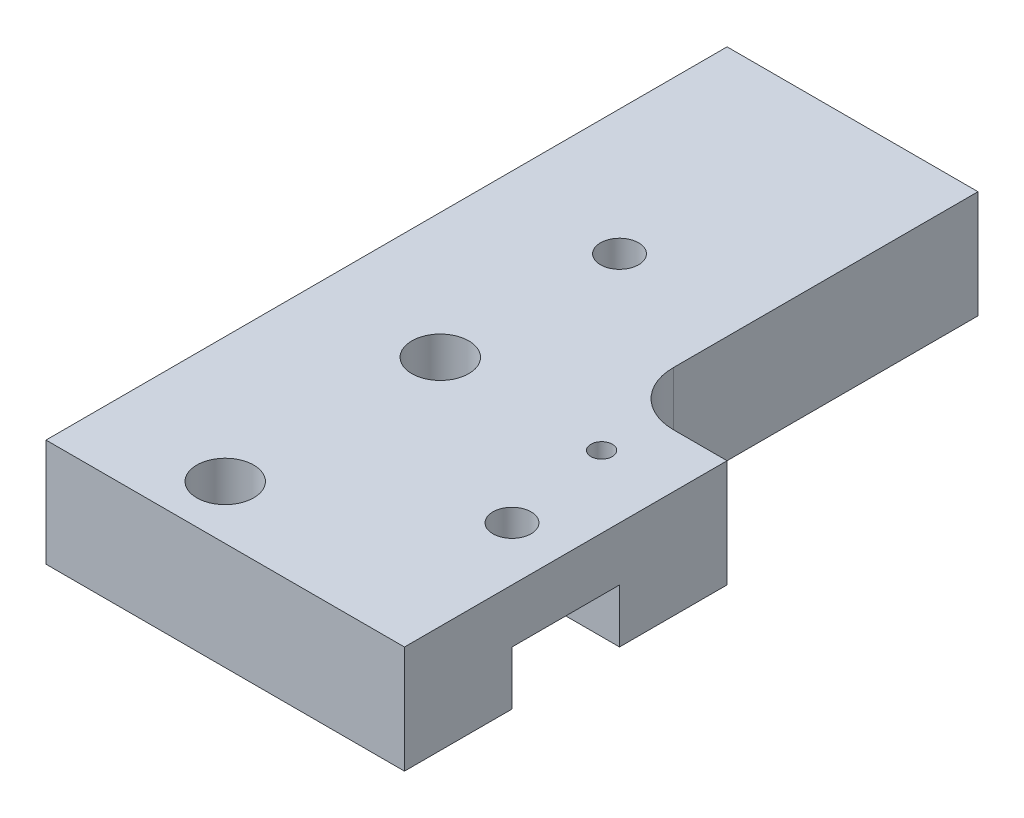
SolidWorks part; units mm, degrees
material "6061-T6 (SS)"
ref_plane "Front" through (0, 0, 0) normal (0, 0, 1) x (1, 0, 0)
ref_plane "Top" through (0, 0, 0) normal (0, 1, 0) x (1, 0, 0)
ref_plane "Right" through (0, 0, 0) normal (1, 0, 0) x (0, 0, -1)
sketch "Sketch1" plane through (0, 0, 0) normal (0, 1, 0) x (1, 0, 0)
  line L1 (-31.75, -28.575) -> (31.75, -28.575)
  line L2 (-31.75, -28.575) -> (-31.75, 28.575)
  line L3 (-31.75, 28.575) -> (31.75, 28.575)
  line L4 (31.75, -28.575) -> (31.75, 28.575)
  line L5 (-31.75, -28.575) -> (31.75, 28.575) construction
  line L6 (-31.75, 28.575) -> (31.75, -28.575) construction
  point P0 (0, 0)
  dimension "D1" = 63.5
  dimension "D2" = 57.15
extrude "Boss-Extrude1" add sketch "Sketch1" along normal blind 19.05
sketch "Sketch2" plane through (0, 0, 0) normal (0, -1, 0) x (1, 0, 0)
  line L0 (31.75, 28.575) -> (31.75, -28.575) construction
  line L1 (-31.75, -9.525) -> (31.75, -9.525)
  line L2 (-31.75, -9.525) -> (-31.75, 9.525)
  line L3 (-31.75, 9.525) -> (31.75, 9.525)
  line L4 (31.75, -9.525) -> (31.75, 9.525)
  line L5 (-31.75, -9.525) -> (31.75, 9.525) construction
  line L6 (-31.75, 9.525) -> (31.75, -9.525) construction
  point P0 (0, 0)
  dimension "D1" = 19.05
extrude "Cut-Extrude1" cut sketch "Sketch2" against normal blind 9.525
sketch "Sketch3" plane through (0, 0, 0) normal (0, -1, 0) x (1, 0, 0)
  line L0 (-31.75, 28.575) -> (31.75, 28.575) construction
  line L1 (3.175, 28.575) -> (15.875, 28.575)
  line L2 (3.175, 28.575) -> (3.175, -28.575)
  line L3 (3.175, -28.575) -> (15.875, -28.575)
  line L4 (15.875, 28.575) -> (15.875, -28.575)
  line L5 (31.75, -28.575) -> (-31.75, -28.575) construction
  line L6 (31.75, 28.575) -> (31.75, 9.525) construction
  dimension "D1" = 12.7
  dimension "D2" = 15.875
extrude "Cut-Extrude2" [suppressed] cut sketch "Sketch3" against normal up to surface (6.35 mm away) up to face at (0, 9.525, 0)
sketch "Sketch4" plane through (0, 9.525, 0) normal (0, -1, 0) x (1, 0, 0)
  line L0 (31.75, 0) -> (22.225, 0) construction
  line L1 (31.75, -9.525) -> (31.75, 9.525) construction
  line L2 (9.525, 28.575) -> (9.525, 19.05) construction
  dimension "D1" = 9.525
sketch "Sketch7" plane through (0, 0, 0) normal (0, 1, 0) x (1, 0, 0)
  line L0 (-9.525, 28.575) -> (-9.525, 19.05) construction
  line L1 (31.75, 28.575) -> (-31.75, 28.575) construction
  line L2 (-9.525, 19.05) -> (-9.525, 9.525) construction
  line L3 (-9.525, -19.05) -> (-9.525, -28.575) construction
  line L4 (-31.75, -28.575) -> (31.75, -28.575) construction
  line L5 (-31.75, 28.575) -> (-31.75, -28.575) construction
  line L10 (-31.75, 9.525) -> (31.75, 9.525) construction
  dimension "D2" = 22.225
hole_wizard "3/8 Clearance Hole1" positions "Sketch9" profile "Sketch8" hole size "3/8" standard "ANSI Inch" end condition through all
sketch "Sketch9" plane through (0, 19.05, 0) normal (0, 1, 0) x (1, 0, 0)
  point P0 (-9.525, 19.05)
  point P3 (-9.525, -19.05)
sketch "Sketch8" plane through (-9.525, 19.05, -19.05) normal (1, 0, 0) x (0, 0, 1)
  line L0 (0, 0) -> (0, 19.05)
  line L1 (0, 19.05) -> (5.0419, 19.05)
  line L2 (5.0419, 19.05) -> (5.0419, 0)
  line L5 (5.0419, 0) -> (0, 0)
  line L11 (0, -6.35) -> (0, 107.95) construction
  dimension "Thru Hole Dia." = 10.0838
  dimension "Thru Hole Depth" = 19.05
sketch "Sketch10" plane through (0, 0, -28.575) normal (0, 0, -1) x (-1, 0, 0)
  line L1 (31.75, 19.05) -> (-31.75, 19.05)
  line L2 (31.75, 19.05) -> (31.75, 0)
  line L3 (31.75, 0) -> (-31.75, 0)
  line L4 (-31.75, 19.05) -> (-31.75, 0)
extrude "Boss-Extrude2" add sketch "Sketch10" along normal blind 63.5
sketch "Sketch11" plane through (0, 0, 0) normal (0, -1, 0) x (1, 0, 0)
  line L0 (31.75, -92.075) -> (-31.75, -92.075) construction
  line L1 (-19.05, -92.075) -> (0, -92.075)
  line L2 (-19.05, -92.075) -> (-19.05, -31.75)
  line L3 (-19.05, -31.75) -> (0, -31.75)
  line L4 (0, -92.075) -> (0, -31.75)
  line L5 (0, -39.2296) -> (-9.525, -39.2296) construction
  line L7 (-31.75, -9.525) -> (-31.75, 9.525) construction
  line L8 (-9.525, -28.575) -> (-9.525, -39.2296) construction
  line L9 (-9.525, -28.575) -> (-9.525, -19.05) construction
  circle A0 centre (-9.525, -19.05) radius 5.0419 construction
  dimension "D1" = 9.525
  dimension "D2" = 12.7
extrude "Cut-Extrude3" cut sketch "Sketch11" against normal up to surface (9.525 mm away) up to face at (0, 9.525, 0)
fillet "Fillet1" radius 6.35 2 edges at (0, 4.7625, -31.75) (-19.05, 4.7625, -31.75)
sketch "Sketch12" plane through (0, 9.525, 0) normal (0, -1, 0) x (1, 0, 0)
  line L0 (0, -38.1) -> (-9.525, -38.1) construction
  line L1 (-9.525, -38.1) -> (-9.525, -50.8) construction
  arc A0 (0, -38.1) -> (-6.35, -31.75) centre (-6.35, -38.1) ccw construction
  dimension "D1" = 9.525
  dimension "D2" = 12.7
hole_wizard "1/4 Clearance Hole1" positions "Sketch6" profile "Sketch5" hole size "1/4" standard "ANSI Inch" end condition through all
sketch "Sketch6" plane through (0, 9.525, 0) normal (0, -1, 0) x (-1, 0, 0)
  point P3 (-22.225, 0)
  point P9 (9.525, 50.8)
sketch "Sketch5" plane through (22.225, 9.525, 0) normal (1, 0, 0) x (0, 0, -1)
  line L0 (0, 0) -> (0, 9.525)
  line L1 (0, 9.525) -> (3.3782, 9.525)
  line L2 (3.3782, 9.525) -> (3.3782, 0)
  line L5 (3.3782, 0) -> (0, 0)
  line L11 (0, -6.35) -> (0, 107.95) construction
  dimension "Thru Hole Dia." = 6.7564
  dimension "Thru Hole Depth" = 9.525
sketch "Sketch13" plane through (0, 0, 0) normal (0, -1, 0) x (1, 0, 0)
  line L0 (12.7, -92.075) -> (12.7, -28.575)
  line L1 (31.75, -92.075) -> (0, -92.075) construction
  line L2 (12.7, -28.575) -> (31.75, -28.575)
  line L3 (31.75, -9.525) -> (31.75, -92.075) construction
  line L4 (31.75, -28.575) -> (31.75, -92.075)
  line L5 (31.75, -92.075) -> (12.7, -92.075)
  line L6 (-31.75, 28.575) -> (31.75, 28.575) construction
  dimension "D1" = 19.05
  dimension "D2" = 57.15
extrude "Cut-Extrude5" cut sketch "Sketch13" against normal through all
fillet "Fillet2" radius 9.525 1 edges at (12.7, 9.525, -28.575)
sketch "Sketch14" plane through (0, 19.05, 0) normal (0, 1, 0) x (1, 0, 0)
  line L0 (31.75, 19.05) -> (19.05, 19.05) construction
  line L1 (31.75, -28.575) -> (31.75, 28.575) construction
  line L2 (-31.75, -28.575) -> (31.75, -28.575) construction
  dimension "D1" = 12.7
  dimension "D2" = 47.625
hole_wizard "#10-24 Tapped Hole1" positions "Sketch16" profile "Sketch15" tap size "#10-24" standard "ANSI Inch" end condition through all
sketch "Sketch16" plane through (0, 19.05, 0) normal (0, 1, 0) x (1, 0, 0)
  point P0 (19.05, 19.05)
sketch "Sketch15" plane through (19.05, 19.05, -19.05) normal (1, 0, 0) x (0, 0, 1)
  line L0 (0, 0) -> (0, 19.05)
  line L1 (0, 19.05) -> (1.8986, 19.05)
  line L2 (1.8986, 19.05) -> (1.8986, 0)
  line L5 (1.8986, 0) -> (0, 0)
  line L11 (0, -6.35) -> (0, 107.95) construction
  dimension "Thru Tap Drill Dia." = 3.7973
  dimension "Thru Tap Drill Depth" = 19.05
cosmetic thread "Hole Thread1" parameters "D2"=4.826
